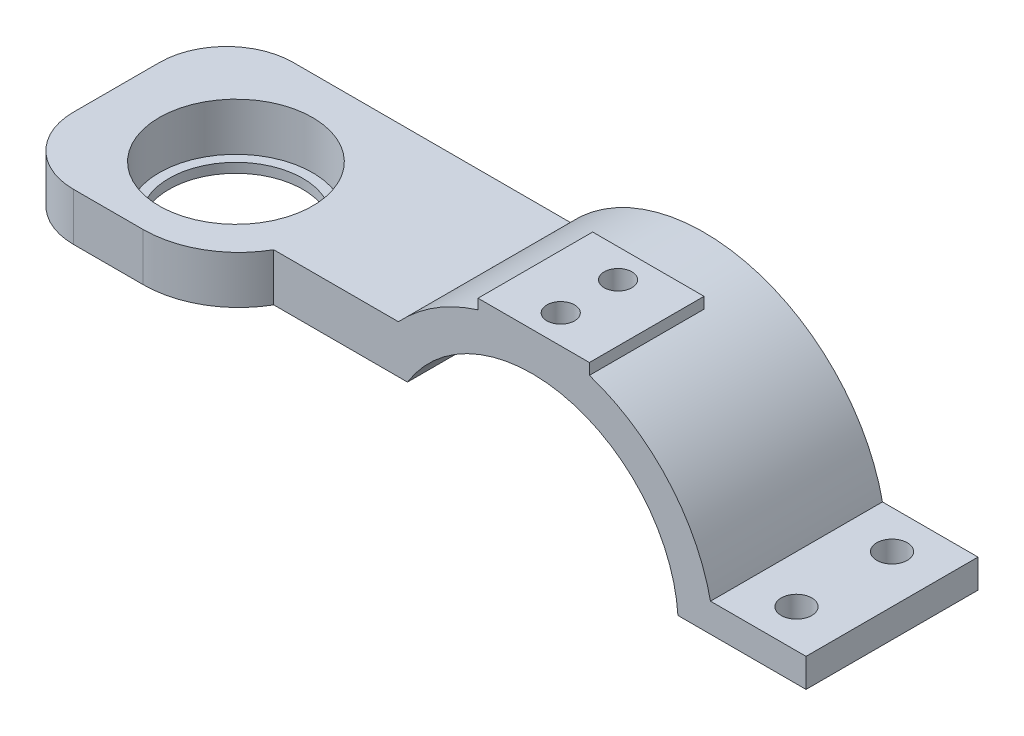
SolidWorks part; units mm, degrees
ref_plane "Front Plane" through (0, 0, 0) normal (0, 0, 1) x (1, 0, 0)
ref_plane "Top Plane" through (0, 0, 0) normal (0, 1, 0) x (1, 0, 0)
ref_plane "Right Plane" through (0, 0, 0) normal (1, 0, 0) x (0, 0, -1)
sketch "Sketch1" plane through (0, 0, 0) normal (0, 0, 1) x (1, 0, 0)
  line L0 (15.2673, 1) -> (28.6765, 1)
  line L1 (18.6765, 4) -> (28.6765, 4)
  line L2 (28.6765, 4) -> (28.6765, 1)
  line L3 (0, 0) -> (-50, 0) construction
  line L4 (-13.0419, 8) -> (-50, 8)
  line L5 (-50, 8) -> (-50, 13)
  line L6 (-50, 13) -> (-13.9932, 13)
  line L7 (0, 0) -> (28.6765, 0) construction
  arc A0 (15.2673, 1) -> (-13.0419, 8) centre (0, 0) ccw
  arc A1 (18.6765, 4) -> (-13.9932, 13) centre (0, 0) ccw
  dimension "D1" = 15.3
  dimension "D4" = 19.1
  dimension "D2" = 3
  dimension "D3" = 10
  dimension "D5" = 5
  dimension "D6" = 8
  dimension "D7" = 50
  dimension "D8" = 1
extrude "Boss-Extrude1" add sketch "Sketch1" along normal blind 18
sketch "Sketch3" plane through (0, 4, 0) normal (0, 1, 0) x (1, 0, 0)
  line L0 (28.6765, -18) -> (18.6765, -18) construction
  line L1 (23.6765, -14) -> (23.6765, -18) construction
  line L2 (23.6765, -4) -> (23.6765, 0) construction
  line L3 (28.6765, 0) -> (18.6765, 0) construction
  circle A0 centre (23.6765, -4) radius 1.6
  circle A1 centre (23.6765, -14) radius 1.6
  point P6 (23.6765, -18)
  dimension "D1" = 3.2
  dimension "D2" = 10
extrude "Cut-Extrude1" cut sketch "Sketch3" against normal through all
sketch "Sketch5" plane through (0, 8, 0) normal (0, -1, 0) x (1, 0, 0)
  line L0 (-50, 18) -> (-50, 23)
  line L2 (-50, 18) -> (-13.0419, 18) construction
  line L3 (-27.0419, 18) -> (-50, 18)
  line L4 (-27.0419, 18) -> (-27.0419, 23)
  line L5 (-27.0419, 23) -> (-50, 23)
  line L6 (-13.0419, 18) -> (-13.0419, 0) construction
  dimension "D2" = 5
  dimension "D3" = 14
extrude "Boss-Extrude2" add sketch "Sketch5" against normal up to surface (5 mm away) up to face at (-31.9966, 13, 9)
sketch "Sketch6" plane through (0, 13, 0) normal (0, 1, 0) x (1, 0, 0)
  line L0 (-13.9932, 0) -> (-50, 0) construction
  line L1 (-50, -23) -> (-50, 0) construction
  circle A0 centre (-37, -12) radius 8.025
  dimension "D1" = 16.05
  dimension "D2" = 12
  dimension "D3" = 13
extrude "Cut-Extrude2" cut sketch "Sketch6" against normal through all
sketch "Sketch7" plane through (0, 8, 0) normal (0, -1, 0) x (1, 0, 0)
  circle A0 centre (-37, 12) radius 9
  circle A1 centre (-37, 12) radius 7
  dimension "D1" = 18
  dimension "D2" = 14
extrude "Boss-Extrude3" add sketch "Sketch7" along normal blind 1
fillet "Fillet1" radius 7 2 edges at (-50, 10.5, 0) (-50, 10.5, 23)
fillet "Fillet2" radius 10 1 edges at (-27.0419, 10.5, 23)
sketch "Sketch8" plane through (0, 0, 18) normal (0, 0, 1) x (1, 0, 0)
  line L0 (6, 18.1331) -> (6, 19.3)
  line L1 (6, 19.3) -> (-5.66, 19.3)
  line L4 (-5.66, 19.3) -> (-5.66, 18.2421)
  line L5 (-5.66, 18.2421) -> (6, 18.1331)
  arc A0 (18.6765, 4) -> (-13.9932, 13) centre (0, 0) ccw construction
  dimension "D2" = 19.3
  dimension "D1" = 6
  dimension "D3" = 11.66
extrude "Boss-Extrude4" add sketch "Sketch8" against normal blind 12
sketch "Sketch9" plane through (0, 19.3, 0) normal (0, 1, 0) x (1, 0, 0)
  line L2 (0, -18) -> (0, -15) construction
  line L3 (0, -15) -> (0, -9) construction
  line L4 (0, -9) -> (0, -6) construction
  line L6 (6, -6) -> (-5.66, -6) construction
  line L7 (6, -18) -> (-5.66, -18) construction
  circle A0 centre (0, -15) radius 1.45
  circle A1 centre (0, -9) radius 1.45
  dimension "D1" = 2.9
  dimension "D2" = 6
  dimension "D3" = 6
extrude "Cut-Extrude3" cut sketch "Sketch9" against normal blind 4.15
